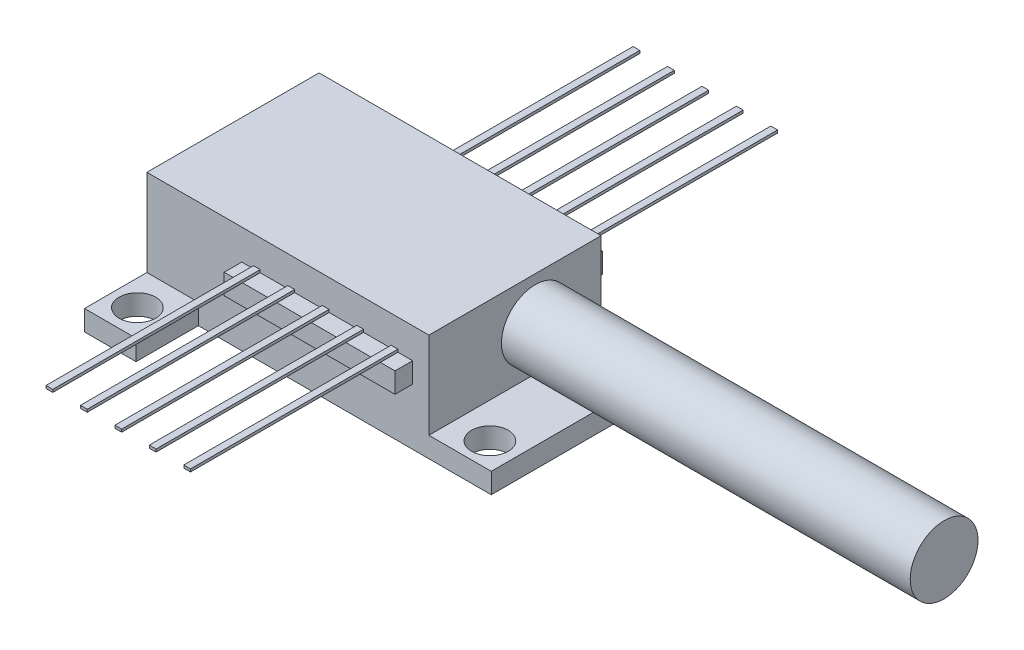
SolidWorks part; units mm, degrees
ref_plane "Front Plane" through (0, 0, 0) normal (0, 0, 1) x (1, 0, 0)
ref_plane "Top Plane" through (0, 0, 0) normal (0, 1, 0) x (1, 0, 0)
ref_plane "Right Plane" through (0, 0, 0) normal (1, 0, 0) x (0, 0, -1)
sketch "Sketch1" plane through (0, 0, 0) normal (0, 1, 0) x (1, 0, 0)
  line L1 (-10.4, -6.35) -> (10.4, -6.35)
  line L2 (-10.4, -6.35) -> (-10.4, 6.35)
  line L3 (-10.4, 6.35) -> (10.4, 6.35)
  line L4 (10.4, -6.35) -> (10.4, 6.35)
  line L5 (-10.4, -6.35) -> (10.4, 6.35) construction
  line L6 (-10.4, 6.35) -> (10.4, -6.35) construction
  point P0 (0, 0)
  dimension "D1" = 12.7
  dimension "D2" = 20.8
extrude "Boss-Extrude1" add sketch "Sketch1" along normal blind 6.4
sketch "Sketch3" plane through (0, 0, 0) normal (0, -1, 0) x (1, 0, 0)
  line L0 (-10.4, 6.35) -> (10.4, 6.35) construction
  line L1 (-10.4, 10.95) -> (-6.6, 10.95)
  line L2 (-10.4, 10.95) -> (-10.4, -10.95)
  line L3 (-10.4, 0) -> (15, 0) construction
  line L4 (15, 6.35) -> (15, -6.35)
  line L5 (-6.6, -6.35) -> (15, -6.35)
  line L6 (-6.6, 10.95) -> (-6.6, 6.35)
  line L7 (-6.6, 6.35) -> (15, 6.35)
  line L8 (-6.6, -10.95) -> (-6.6, -6.35)
  line L9 (-10.4, -10.95) -> (-6.6, -10.95)
  dimension "D1" = 25.4
  dimension "D2" = 10.95
  dimension "D3" = 3.8
extrude "Boss-Extrude2" add sketch "Sketch3" along normal blind 1.5
sketch "Sketch5" plane through (0, -1.5, 0) normal (0, -1, 0) x (1, 0, 0)
  line L0 (15, -6.35) -> (15, 6.35) construction
  line L1 (-10.4, 10.95) -> (-10.4, 6.35) construction
  circle A0 centre (-8.5, 8.95) radius 1.35
  circle A1 centre (13, 4.45) radius 1.35
  dimension "D1" = 2.7
  dimension "D2" = 4.45
  dimension "D3" = 2
  dimension "D4" = 8.95
  dimension "D5" = 1.9
extrude "Cut-Extrude1" cut sketch "Sketch5" against normal through all
mirror "Mirror3" about plane through (0, 0, 0) normal (0, 0, 1) of "Cut-Extrude1"
sketch "Sketch6" plane through (-10.4, 0, 0) normal (-1, 0, 0) x (0, 0, 1)
  line L0 (6.35, 6.4) -> (6.35, 0) construction
  line L1 (10.95, -1.5) -> (-10.95, -1.5) construction
  point P0 (1.85, 3.3)
  dimension "D1" = 4.5
  dimension "D2" = 4.8
ref_point "laser_out"
ref_axis "laser" through (-10.4, 3.3, 1.85) along (-1, 0, 0)
sketch "Sketch7" plane through (10.4, 0, 0) normal (1, 0, 0) x (0, 0, -1)
  line L0 (6.35, 6.4) -> (6.35, 0) construction
  line L1 (6.35, -1.5) -> (-6.35, -1.5) construction
  point P0 (1.5, 3.2)
  dimension "D1" = 4.85
  dimension "D2" = 4.7
ref_point "fiber_out"
ref_axis "fiber" through (10.4, 3.2, -1.5) along (1, 0, 0)
sketch "Sketch8" plane through (10.4, 0, 0) normal (1, 0, 0) x (0, 0, -1)
  circle A0 centre (1.5, 3.2) radius 2.5
  dimension "D1" = 5
extrude "Boss-Extrude3" add sketch "Sketch8" along normal blind 30.15
ref_plane "Plane1" through (0, 2.665, 0) normal (0, -1, 0) x (-1, 0, 0)
sketch "Sketch9" plane through (0, 2.665, 0) normal (0, -1, 0) x (-1, 0, 0)
  line L0 (10.4, -6.35) -> (-10.4, -6.35) construction
  line L1 (3.4, -6.35) -> (-9.2, -6.35)
  line L2 (3.4, -6.35) -> (3.4, -7.65)
  line L3 (3.4, -7.65) -> (-9.2, -7.65)
  line L4 (-9.2, -6.35) -> (-9.2, -7.65)
  line L6 (10.4, 6.35) -> (10.4, -6.35) construction
  line L7 (-10.4, -6.35) -> (-10.4, 6.35) construction
  dimension "D1" = 7.65
  dimension "D2" = 1.2
  dimension "D3" = 7
extrude "Boss-Extrude4" add sketch "Sketch9" against normal blind 1.5
sketch "Sketch10" plane through (0, 4.165, 0) normal (0, 1, 0) x (1, 0, 0)
  line L0 (-3.4, -6.35) -> (9.2, -6.35) construction
  line L1 (7.62, -6.35) -> (8.12, -6.35)
  line L2 (7.62, -6.35) -> (7.62, -21.65)
  line L3 (7.62, -21.65) -> (8.12, -21.65)
  line L4 (8.12, -6.35) -> (8.12, -21.65)
  line L5 (7.87, -6.35) -> (7.87, -21.65) construction
  line L6 (10.4, -6.35) -> (10.4, 6.35) construction
  dimension "D1" = 0.5
  dimension "D2" = 21.65
  dimension "D3" = 2.53
extrude "Boss-Extrude5" add sketch "Sketch10" along normal blind 0.2
pattern_linear "LPattern1" count 5 spacing 2.54 along (-1, 0, 0) of "Boss-Extrude5"
mirror "Mirror2" about plane through (0, 0, 0) normal (0, 0, 1) of "Boss-Extrude4", "Boss-Extrude5", "LPattern1"
